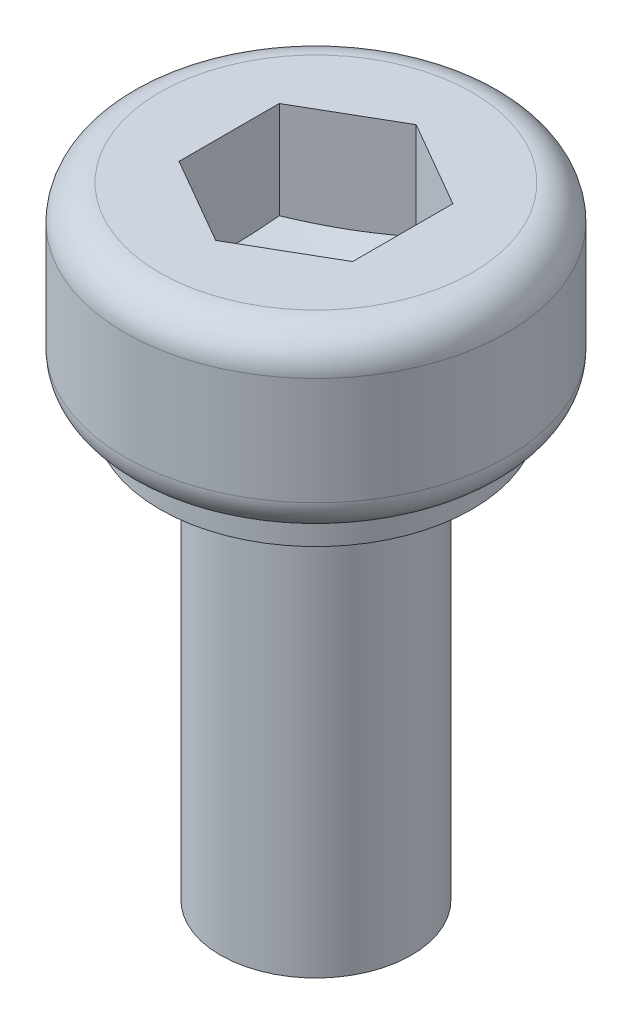
SolidWorks part; units mm, degrees
ref_plane "Front Plane" through (0, 0, 0) normal (0, 0, 1) x (1, 0, 0)
ref_plane "Top Plane" through (0, 0, 0) normal (0, 1, 0) x (1, 0, 0)
ref_plane "Right Plane" through (0, 0, 0) normal (1, 0, 0) x (0, 0, -1)
sketch "Sketch1" plane through (0, 0, 0) normal (0, 0, 1) x (1, 0, 0)
  line L0 (0, 4.0942) -> (0, -5.2249) construction
  line L1 (0, 4.475) -> (2.25, 4.475)
  line L2 (2.75, 3.975) -> (2.75, 2.425)
  line L3 (2.25, 1.525) -> (1.375, 1.525)
  line L4 (1.375, 1.525) -> (1.375, -4.475)
  line L5 (1.375, -4.475) -> (0, -4.475)
  line L6 (0, -4.475) -> (0, 4.475)
  line L7 (2.25, 1.525) -> (2.25, 1.925)
  line L8 (2.75, 1.525) -> (2.25, 1.525) construction
  line L9 (2.75, 2.425) -> (2.75, 1.525) construction
  line L10 (2.75, 4.475) -> (2.75, 3.975) construction
  line L11 (2.25, 4.475) -> (2.75, 4.475) construction
  arc A0 (2.25, 1.925) -> (2.75, 2.425) centre (2.25, 2.425) ccw
  arc A1 (2.25, 4.475) -> (2.75, 3.975) centre (2.25, 3.975) cw
  point P5 (0, 0)
  point P17 (0, 0)
  point P18 (0, 0)
  point P19 (2.25, 2.4541)
  dimension "D5" = 0.5
  dimension "D1" = 6
  dimension "D2" = 1.375
  dimension "D3" = 2.95
  dimension "D4" = 2.75
  dimension "D6" = 0.4
revolve "Revolve1" add sketch "Sketch1" angle 360 about L0
sketch "Sketch2" plane through (0, 4.475, 0) normal (0, 1, 0) x (1, 0, 0)
  line L1 (0, 1.4434) -> (-1.25, 0.7217)
  line L2 (-1.25, 0.7217) -> (-1.25, -0.7217)
  line L3 (-1.25, -0.7217) -> (0, -1.4434)
  line L4 (0, -1.4434) -> (1.25, -0.7217)
  line L5 (1.25, -0.7217) -> (1.25, 0.7217)
  line L6 (1.25, 0.7217) -> (0, 1.4434)
  circle A0 centre (0, 0) radius 1.25 construction
  dimension "D1" = 2.5
extrude "Boss-Extrude1" add sketch "Sketch2" against normal blind 2 separate body
sketch "Sketch3" plane through (0, 0, 0) normal (1, 0, 0) x (0, 0, -1)
  line L0 (0, 2.875) -> (0.4, 2.875)
  line L1 (0.4, 2.875) -> (1.4434, 3.075)
  line L2 (1.4434, 2.475) -> (1.4434, 4.475) construction
  line L3 (1.4434, 3.075) -> (1.4434, 2.475)
  line L4 (1.4434, 2.475) -> (0, 2.475)
  line L5 (-0.7217, 2.475) -> (0.7217, 2.475) construction
  line L6 (0, 2.475) -> (0, 2.875)
  line L7 (-0.7217, 4.475) -> (0.7217, 4.475) construction
  dimension "D1" = 1.6
  dimension "D2" = 1.4
  dimension "D3" = 0.4
revolve "Cut-Revolve1" cut sketch "Sketch3" angle 360 about L6
combine bodies "Combine1" operation type subtract main body 101 bodies to subtract 104
equation "\"Length\"= 6mm"
equation "\"D1@Sketch1\"=\"Length\""
equation "\"ThreadDiam\"= 2.75"
equation "\"D2@Sketch1\"=\"ThreadDiam\"/2"
equation "\"HeadHeight\"=2.95"
equation "\"D3@Sketch1\"=\"HeadHeight\""
equation "\"HeadDiam\"= 5.5"
equation "\"D4@Sketch1\"=\"HeadDiam\"/2"
equation "\"HexSize\"=2.5"
equation "\"D1@Sketch2\"=\"HexSize\""
